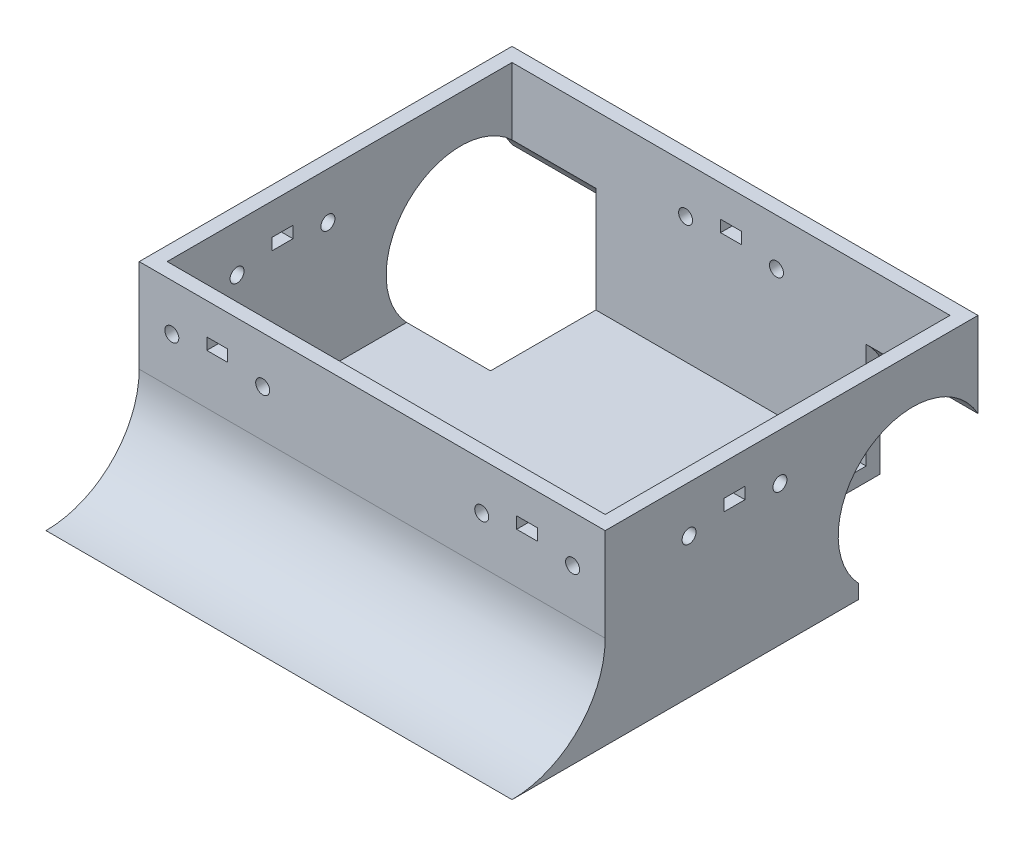
SolidWorks part; units mm, degrees
ref_plane "Plano frontal" through (0, 0, 0) normal (0, 0, 1) x (1, 0, 0)
ref_plane "Plano superior" through (0, 0, 0) normal (0, 1, 0) x (1, 0, 0)
ref_plane "Plano direito" through (0, 0, 0) normal (1, 0, 0) x (0, 0, -1)
sketch "Esboço1" plane through (0, 0, 0) normal (0, 1, 0) x (1, 0, 0)
  line L1 (-50, -50) -> (50, -50)
  line L2 (-50, -50) -> (-50, 50)
  line L3 (-50, 50) -> (50, 50)
  line L4 (50, -50) -> (50, 50)
  line L5 (-50, -50) -> (50, 50) construction
  line L6 (-50, 50) -> (50, -50) construction
  point P0 (0, 0)
  dimension "D1" = 100
  dimension "D2" = 100
extrude "Ressalto-extrusão1" add sketch "Esboço1" along normal mid plane 40
sketch "Esboço2" plane through (0, 0, 0) normal (1, 0, 0) x (0, 0, -1)
  line L0 (-50, 20) -> (-50, -20) construction
  line L1 (-50, 20) -> (-30, 20)
  line L2 (-50, 20) -> (50, 20) construction
  line L3 (-30, 20) -> (-30, 0)
  circle A0 centre (-50, 0) radius 20
extrude "Corte-extrusão1" cut sketch "Esboço2" against normal through all both and the other way through all contours A0 L3 L1 | A0 region at (0, 15.5326, 34.4674) region at (0, 0, 50)
sketch "Esboço3" plane through (0, 0, 0) normal (0, 1, 0) x (1, 0, 0)
  line L0 (-50, 50) -> (-50, -30) construction
  line L1 (-47, 47) -> (47, 47)
  line L2 (-47, 47) -> (-47, -27)
  line L3 (-47, -27) -> (47, -27)
  line L4 (47, 47) -> (47, -27)
  line L5 (-47, 47) -> (47, -27) construction
  line L6 (-47, -27) -> (47, 47) construction
  line L7 (50, 50) -> (-50, 50) construction
  line L8 (50, -30) -> (50, 50) construction
  line L9 (-50, -30) -> (50, -30) construction
  point P0 (0, 10)
  dimension "D1" = 3
  dimension "D2" = 3
  dimension "D3" = 3
  dimension "D4" = 3
extrude "Corte-extrusão2" cut sketch "Esboço3" along normal through all
sketch "Esboço5" plane through (0, 0, 0) normal (0, 1, 0) x (1, 0, 0)
  line L1 (-47, 47) -> (47, 47)
  line L2 (-47, 47) -> (-47, -27)
  line L3 (-47, -27) -> (47, -27)
  line L4 (47, 47) -> (47, -27)
extrude "Corte-extrusão3" cut sketch "Esboço5" against normal offset from surface (17 mm away) 3 up to face at (0, -20, 0)
sketch "Esboço6" plane through (0, 0, 0) normal (1, 0, 0) x (0, 0, -1)
  line L0 (47, -20) -> (47, -17) construction
  line L1 (-50, -20) -> (50, -20) construction
  line L2 (50, 20) -> (50, -20) construction
  line L3 (35.0734, -7) -> (47, -7) construction
  line L4 (35.0734, -7) -> (35.0734, -17) construction
  line L5 (35.0734, -17) -> (47, -17) construction
  line L6 (47, -7) -> (47, -17) construction
  line L7 (35.0734, -7) -> (47, -17) construction
  line L8 (35.0734, -17) -> (47, -7) construction
  line L9 (36, -22) -> (52, -22)
  line L10 (52, -22) -> (52, -6)
  circle A0 centre (36, -6) radius 16
  point P5 (41.0367, -12)
  dimension "D5" = 32
  dimension "D7" = 14
  dimension "D1" = 3
  dimension "D2" = 3
  dimension "D3" = 10
  dimension "D4" = 11.9266
  dimension "D6" = 14
extrude "Corte-extrusão4" cut sketch "Esboço6" against normal blind 21 from surface contours A0 | A0 L9 L10 region at (0, -18.4261, -48.4261) region at (0, -6, -36) starting at face at (50, -0.8284, 1.1716)
extrude "Corte-extrusão5" cut sketch "Esboço6<4>" along normal blind 21 from surface contours A0 L9 L10 | A0 region at (0, -18.4261, -48.4261) region at (0, -6, -36) starting at face at (-50, -0.8284, 1.1716)
sketch "Esboço6<4>" plane through (0, 0, 0) normal (1, 0, 0) x (0, 0, -1) same geometry as "Esboço6"
sketch "Esboço7" plane through (0, 0, 0) normal (0, 1, 0) x (1, 0, 0)
  line L0 (-29, 24.381) -> (-50, 24.381)
  line L1 (-47, 24.381) -> (-29, 24.381) construction
  line L2 (-50, 50) -> (-50, -30) construction
  line L3 (-50, 24.381) -> (-50, 28.254)
  line L4 (-50, 28.254) -> (-29, 28.254)
  line L5 (-29, 28.254) -> (-29, 24.381)
  line L6 (50, -30) -> (50, 50) construction
  line L7 (29, 28.254) -> (50, 28.254)
  line L8 (29, 28.254) -> (29, 24.381)
  line L9 (29, 24.381) -> (50, 24.381)
  line L10 (50, 28.254) -> (50, 24.381)
extrude "Corte-extrusão6" cut sketch "Esboço7" against normal blind 21
sketch "Esboço8" plane through (0, 0, 0) normal (0, 0, 1) x (1, 0, 0)
  line L0 (-50, 20) -> (-50, 0) construction
  line L1 (-50, 20) -> (50, 20) construction
  line L2 (31, 13.25) -> (35.5, 13.25)
  line L3 (-35.5, 13.25) -> (-31, 13.25)
  line L4 (-35.5, 13.25) -> (-35.5, 10.75)
  line L5 (-35.5, 10.75) -> (-31, 10.75)
  line L6 (-31, 13.25) -> (-31, 10.75)
  line L7 (-35.5, 13.25) -> (-31, 10.75) construction
  line L8 (-35.5, 10.75) -> (-31, 13.25) construction
  line L9 (31, 13.25) -> (31, 10.75)
  line L10 (31, 10.75) -> (35.5, 10.75)
  line L11 (35.5, 13.25) -> (35.5, 10.75)
  line L12 (31, 13.25) -> (35.5, 10.75) construction
  line L13 (31, 10.75) -> (35.5, 13.25) construction
  line L14 (50, 20) -> (50, 0) construction
  circle A0 centre (-43, 10) radius 1.5
  circle A1 centre (-23.5, 10) radius 1.5
  circle A2 centre (23.5, 10) radius 1.5
  circle A3 centre (43, 10) radius 1.5
  point P0 (-33.25, 12)
  point P7 (0, 0)
  point P10 (0, 0)
  point P15 (33.25, 12)
  dimension "D1" = 3
  dimension "D9" = 3
  dimension "D2" = 19.5
  dimension "D3" = 9.75
  dimension "D4" = 0.75
  dimension "D5" = 7
  dimension "D6" = 10
  dimension "D7" = 2.5
  dimension "D8" = 4.5
  dimension "D10" = 19.5
  dimension "D11" = 9.75
  dimension "D12" = 0.75
  dimension "D13" = 2.5
  dimension "D14" = 4.5
  dimension "D15" = 10
  dimension "D16" = 7
extrude "Corte-extrusão8" cut sketch "Esboço8" along normal through all
sketch "Esboço9" plane through (0, 0, 0) normal (0, 0, 1) x (1, 0, 0)
  line L0 (-2.25, 13.25) -> (2.25, 13.25)
  line L1 (-2.25, 13.25) -> (-2.25, 10.75)
  line L2 (-2.25, 10.75) -> (2.25, 10.75)
  line L3 (2.25, 13.25) -> (2.25, 10.75)
  line L4 (-2.25, 13.25) -> (2.25, 10.75) construction
  line L5 (-2.25, 10.75) -> (2.25, 13.25) construction
  line L6 (-50, 10) -> (50, 10) construction
  line L7 (-50, 20) -> (-50, 0) construction
  line L8 (50, 20) -> (50, 0) construction
  line L9 (-50, 20) -> (50, 20) construction
  line L10 (0, 12) -> (0, 10) construction
  circle A0 centre (-9.75, 10) radius 1.5
  circle A1 centre (9.75, 10) radius 1.5
  point P0 (0, 12)
  dimension "D1" = 3
  dimension "D2" = 19.5
  dimension "D3" = 9.75
  dimension "D4" = 0.75
  dimension "D5" = 2.5
  dimension "D6" = 4.5
  dimension "D7" = 10
extrude "Corte-extrusão9" cut sketch "Esboço9" against normal through all
sketch "Esboço10" plane through (0, 0, 0) normal (1, 0, 0) x (0, 0, -1)
  line L0 (-4.5, 13.25) -> (0, 13.25)
  line L1 (-4.5, 13.25) -> (-4.5, 10.75)
  line L2 (-4.5, 10.75) -> (0, 10.75)
  line L3 (0, 13.25) -> (0, 10.75)
  line L4 (-4.5, 13.25) -> (0, 10.75) construction
  line L5 (-4.5, 10.75) -> (0, 13.25) construction
  line L6 (-30, 20) -> (50, 20) construction
  line L7 (-30, 20) -> (-30, 0) construction
  circle A0 centre (-12, 10) radius 1.5
  circle A1 centre (7.5, 10) radius 1.5
  point P0 (-2.25, 12)
  dimension "D1" = 3
  dimension "D2" = 19.5
  dimension "D3" = 9.75
  dimension "D4" = 0.75
  dimension "D5" = 2.5
  dimension "D6" = 4.5
  dimension "D7" = 10
  dimension "D8" = 18
extrude "Corte-extrusão10" cut sketch "Esboço10" against normal through all both and the other way through all
